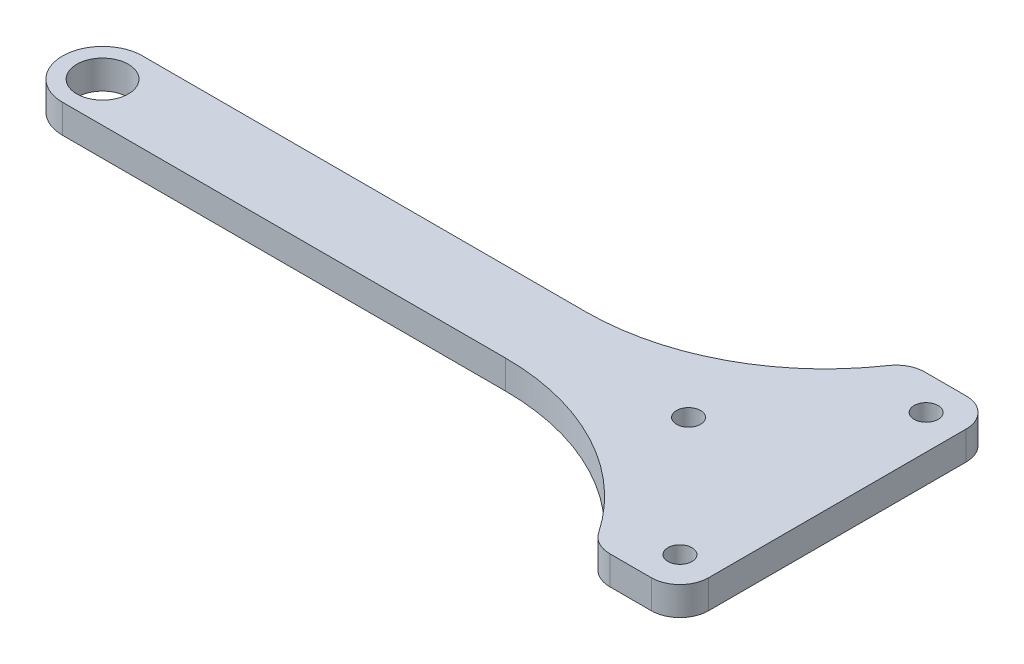
SolidWorks part; units mm, degrees
material "Thornel Mat VMA"
ref_plane "前视基准面" through (0, 0, 0) normal (0, 0, 1) x (1, 0, 0)
ref_plane "上视基准面" through (0, 0, 0) normal (0, 1, 0) x (1, 0, 0)
ref_plane "右视基准面" through (0, 0, 0) normal (1, 0, 0) x (0, 0, -1)
other "Configuration Table"
sketch "草图1" plane through (0, 0, 0) normal (0, 1, 0) x (1, 0, 0)
  line L0 (-102.35, 0) -> (0, 0) construction
  line L1 (-102.35, 7) -> (0, 7)
  line L2 (-102.35, -7) -> (0, -7)
  arc A0 (-102.35, 7) -> (-102.35, -7) centre (-102.35, 0) ccw
  arc A1 (0, -7) -> (0, 7) centre (0, 0) ccw
  circle A2 centre (-102.35, 0) radius 4.5
  circle A3 centre (0, 0) radius 4.5
  point P3 (-51.175, 0)
  dimension "D2" = 9
  dimension "D3" = 7
  dimension "D1" = 102.35
extrude "凸台-拉伸1" add sketch "草图1" along normal blind 5
sketch "草图2" plane through (0, 0, 0) normal (0, -1, 0) x (1, 0, 0)
  line L0 (0, -7) -> (-102.35, -7) construction
  line L1 (11, 27.5) -> (26, 27.5)
  line L2 (11, 27.5) -> (11, -27.5)
  line L3 (11, -27.5) -> (26, -27.5)
  line L4 (26, 27.5) -> (26, -27.5)
  line L5 (-102.35, 7) -> (0, 7) construction
  line L6 (20, -21.5) -> (20, 21.5) construction
  line L7 (-25, 7) -> (-25, -7)
  circle A0 centre (20, -21.5) radius 2.1
  circle A1 centre (20, 21.5) radius 2.1
  arc A2 (-25, 7) -> (11, 27.5) centre (-25, 48.8598) ccw
  arc A3 (11, -27.5) -> (-25, -7) centre (-25, -48.8598) ccw
  circle A5 centre (0, 0) radius 2.1
  point P16 (20, 0)
  line M12 (-102.35, -7) -> (0, -7)
  arc M13 (0, -7) -> (0, 7) centre (0, 0) ccw
  line M14 (0, 7) -> (-102.35, 7)
  circle M16 centre (0, 0) radius 4.5
  dimension "D2" = 4.2
  dimension "D8" = 4.2
  dimension "D1" = 20
  dimension "D3" = 43
  dimension "D4" = 15
  dimension "D5" = 55
  dimension "D6" = 6
  dimension "D7" = 25
extrude "凸台-拉伸2" add sketch "草图2" against normal blind 5 contours A3 L2 A2 M14 M13 M12 | L4 L1 L2 L3 A0 A1 | A5 M16 region at (18.4479, 0, 0) region at (10.3427, 0, 0) region at (-4.3727, 0, 0)
fillet "圆角1" radius 5 4 edges at (11, 2.5, -27.5) (26, 2.5, 27.5) (11, 2.5, 27.5) (26, 2.5, -27.5)
